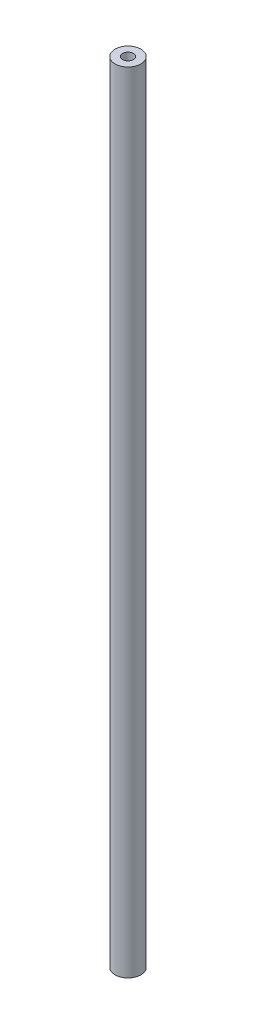
SolidWorks part; units mm, degrees
material "6063-T6"
ref_plane "Płaszczyzna przednia" through (0, 0, 0) normal (0, 0, 1) x (1, 0, 0)
ref_plane "Płaszczyzna górna" through (0, 0, 0) normal (0, 1, 0) x (1, 0, 0)
ref_plane "Płaszczyzna prawa" through (0, 0, 0) normal (1, 0, 0) x (0, 0, -1)
sketch "Szkic1" plane through (0, 0, 0) normal (0, 1, 0) x (1, 0, 0)
  circle A0 centre (0, 0) radius 5
  dimension "D1" = 10
extrude "Dodanie-wyciągnięcie1" add sketch "Szkic1" along normal blind 306
sketch "Szkic2" plane through (0, 0, 0) normal (0, -1, 0) x (-1, 0, 0)
  point P0 (0, 0)
hole_wizard "Tap Drill for M5 Tap1" positions "Szkic2" profile "Szkic3" hole size "M5" standard "ISO"
sketch "Szkic3" plane through (0, 0, 0) normal (1, 0, 0) x (0, 0, -1)
  line L0 (0, 0) -> (0, 31.2618)
  line L1 (0, 31.2618) -> (2.1, 30)
  line L2 (2.1, 30) -> (2.1, 0)
  line L5 (2.1, 0) -> (0, 0)
  line L10 (0, 31.2618) -> (-2.1, 30) construction
  line L11 (0, -6.35) -> (0, 107.95) construction
  dimension "Średnica otworu" = 4.2
  dimension "Głębokość otworu" = 30
  dimension "Kąt wiertła" = 118
sketch "Szkic4" plane through (0, 306, 0) normal (0, 1, 0) x (1, 0, 0)
  point P0 (0, 0)
hole_wizard "Tap Drill for M5 Tap2" positions "Szkic4" profile "Szkic5" hole size "M5" standard "ISO"
sketch "Szkic5" plane through (0, 306, 0) normal (1, 0, 0) x (0, 0, 1)
  line L0 (0, 0) -> (0, 31.2618)
  line L1 (0, 31.2618) -> (2.1, 30)
  line L2 (2.1, 30) -> (2.1, 0)
  line L5 (2.1, 0) -> (0, 0)
  line L10 (0, 31.2618) -> (-2.1, 30) construction
  line L11 (0, -6.35) -> (0, 107.95) construction
  dimension "Średnica otworu" = 4.2
  dimension "Głębokość otworu" = 30
  dimension "Kąt wiertła" = 118
